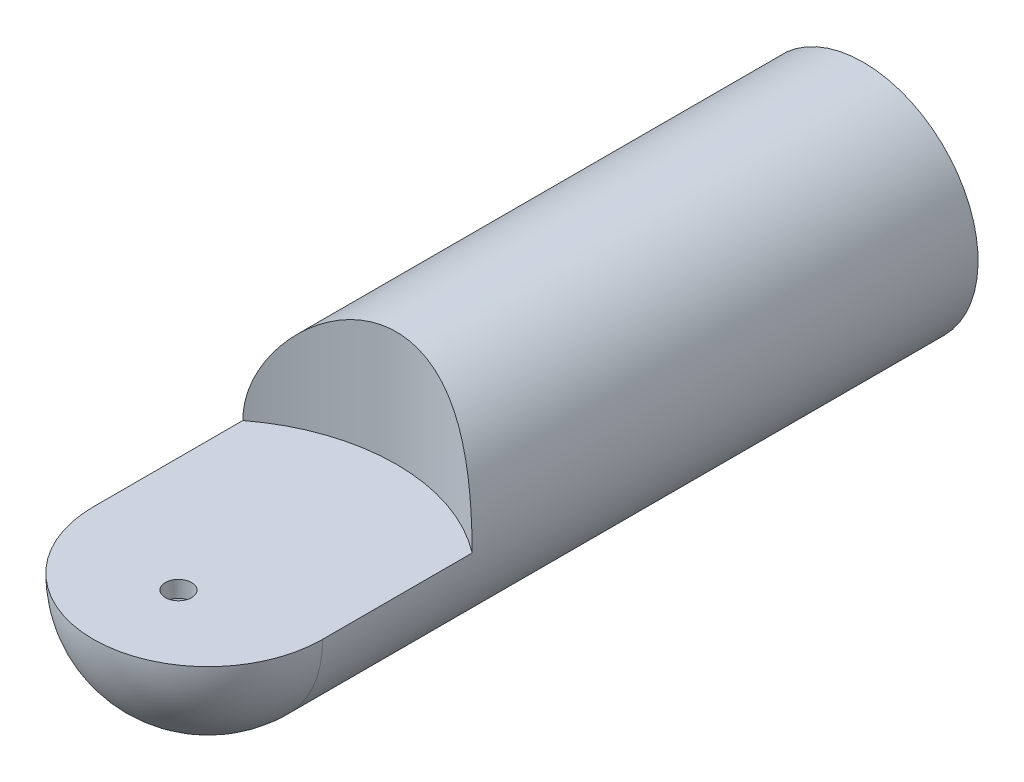
SolidWorks part; units mm, degrees
note: The reader was unsure of these and kept them because the rebuilt part matched: shared geometry of "Sketch5<5>", "Sketch5<7>", "Sketch5<9>".
ref_plane "Front Plane" through (0, 0, 0) normal (0, 0, 1) x (1, 0, 0)
ref_plane "Top Plane" through (0, 0, 0) normal (0, 1, 0) x (1, 0, 0)
ref_plane "Right Plane" through (0, 0, 0) normal (1, 0, 0) x (0, 0, -1)
sketch "Sketch1" plane through (0, 0, 0) normal (0, 1, 0) x (1, 0, 0)
  line L0 (-35, 0) -> (35, 0)
  arc A0 (-35, 0) -> (35, 0) centre (0, 0) ccw
  dimension "D1" = 70
revolve "Revolve1" add sketch "Sketch1" angle 90 about L0
shell "Shell2" thickness 5
sketch "Sketch3" plane through (0, 0, 0) normal (0, 1, 0) x (1, 0, 0)
  line L0 (0, 0) -> (0, -5)
  circle A0 centre (0, -9) radius 4
  dimension "D2" = 8
  dimension "D1" = 5
extrude "Cut-Extrude1" cut sketch "Sketch3" against normal blind 7 contours A0
sketch "Sketch4" plane through (0, 0, 0) normal (0, 0, -1) x (-1, 0, 0)
  line L0 (35, 0) -> (-35, 0) construction
  circle A0 centre (0, 0) radius 35
  circle A1 centre (0, 0) radius 30
extrude "Boss-Extrude1" add sketch "Sketch4" along normal blind 200
sketch "Sketch5" plane through (0, 0, 0) normal (0, 1, 0) x (1, 0, 0)
  line L0 (-35, 0) -> (35, 0)
  line L1 (-35, 45.6207) -> (-35, 48.734)
  line L2 (-35, 0) -> (35, 0)
  line L3 (-35, 0) -> (-35, 45.6207)
  line L4 (-35, 45.6207) -> (35, 45.6207)
  line L5 (35, 0) -> (35, 45.6207)
  line L6 (-35, 200) -> (-35, 0) construction
  line L7 (35, 45.6207) -> (35, 48.734)
  circle A0 centre (0, 0) radius 30
  circle A1 centre (0, 0) radius 35
  circle A2 centre (0, 0) radius 57.5
  circle A3 centre (0, 0) radius 60
  line M3 (-30, 0) -> (-35, 0)
  line M5 (35, 0) -> (30, 0)
  line M6 (30, 0) -> (-30, 0)
  dimension "D1" = 115
  dimension "D2" = 120
extrude "Boss-Extrude3" add sketch "Sketch5" along normal up to surface contours A1 A0 M5 M3
extrude "Cut-Extrude3" cut sketch "Sketch5<5>" along normal blind 80 contours A0 M6
sketch "Sketch5<5>" plane through (0, 0, 0) normal (0, 1, 0) x (1, 0, 0) same geometry as "Sketch5"
sketch "Sketch6" plane through (0, 0, 0) normal (0, 0, -1) x (-1, 0, 0)
  line L1 (-30, 0) -> (30, 0)
  line L2 (-30, 0) -> (-30, -5)
  line L3 (-30, -5) -> (30, -5)
  line L4 (30, 0) -> (30, -5)
extrude "Boss-Extrude4" add sketch "Sketch6" along normal blind 60
extrude "Cut-Extrude4" cut sketch "Sketch5<7>" along normal blind 113 contours A1 A0 M5 M3 | A1 L5 L4 L3 | L4 A2
sketch "Sketch5<7>" plane through (0, 0, 0) normal (0, 1, 0) x (1, 0, 0) same geometry as "Sketch5"
extrude "Boss-Extrude5" add sketch "Sketch5<9>" along normal up to surface contours L7 A3 L1 A2
sketch "Sketch5<9>" plane through (0, 0, 0) normal (0, 1, 0) x (1, 0, 0) same geometry as "Sketch5"
